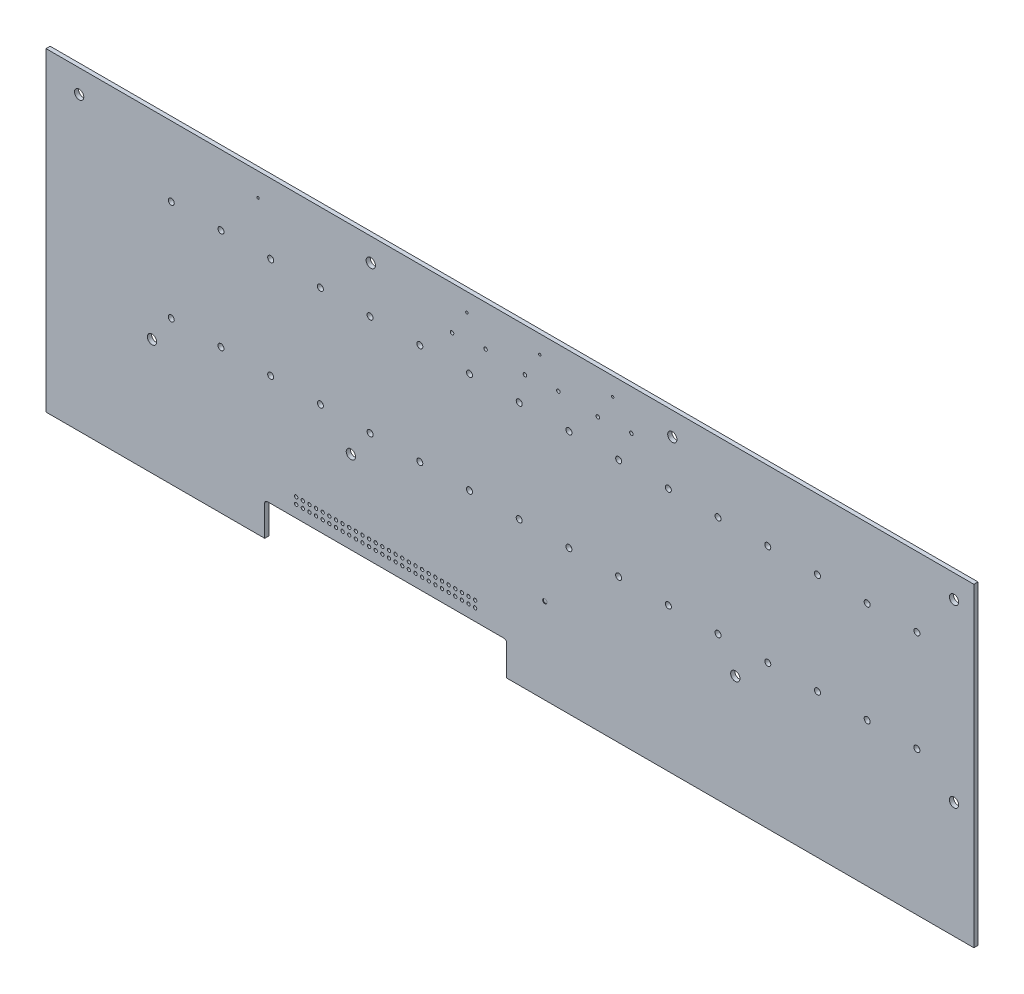
SolidWorks part; units mm, degrees
ref_plane "Front" through (0, 0, 0) normal (0, 0, 1) x (1, 0, 0)
ref_plane "Top" through (0, 0, 0) normal (0, 1, 0) x (1, 0, 0)
ref_plane "Right" through (0, 0, 0) normal (1, 0, 0) x (0, 0, -1)
sketch "Sketch1" plane through (0, 0, 0) normal (0, 0, 1) x (1, 0, 0)
  line L1 (0, 0) -> (355.6, 0)
  line L2 (0, 0) -> (0, -120.65)
  line L3 (0, -120.65) -> (355.6, -120.65)
  line L4 (355.6, 0) -> (355.6, -120.65)
  dimension "D1" = 120.65
  dimension "D2" = 355.6
extrude "Extrude1" add sketch "Sketch1" along normal blind 1.5748
sketch "DSPboard connector holes" plane through (0, 0, 1.5748) normal (0, 0, 1) x (1, 0, 0)
  line L0 (0, -120.65) -> (355.6, -120.65) construction
  line L1 (0, 0) -> (0, -120.65) construction
  circle A0 centre (48.006, -65.532) radius 1.15
  circle A1 centre (48.006, -26.802) radius 1.15
  dimension "D1" = 2.3
  dimension "D4" = 2.3
  dimension "D2" = 55.118
  dimension "D3" = 48.006
  dimension "D5" = 38.73
extrude "Cut-Extrude1" cut sketch "DSPboard connector holes" against normal blind 2.54
pattern_linear "LPattern1" count 16 spacing 19.05 along (1, 0, 0) of "Cut-Extrude1"
sketch "Sketch2" plane through (0, 0, 1.5748) normal (0, 0, 1) x (1, 0, 0)
  line L0 (0, -120.65) -> (355.6, -120.65) construction
  line L1 (0, 0) -> (0, -120.65) construction
  circle A0 centre (12.7, -8.89) radius 1.778
  circle A1 centre (124.46, -8.89) radius 1.778
  circle A2 centre (240.03, -8.89) radius 1.778
  circle A3 centre (347.98, -8.89) radius 1.778
  circle A4 centre (40.64, -76.2) radius 1.778
  circle A5 centre (116.84, -76.2) radius 1.778
  circle A6 centre (264.16, -76.2) radius 1.778
  circle A7 centre (347.98, -76.2) radius 1.778
  dimension "D1" = 3.556
  dimension "D4" = 3.556
  dimension "D5" = 3.556
  dimension "D6" = 3.556
  dimension "D10" = 3.556
  dimension "D11" = 3.556
  dimension "D12" = 3.556
  dimension "D13" = 3.556
  dimension "D2" = 111.76
  dimension "D3" = 12.7
  dimension "D7" = 124.46
  dimension "D8" = 240.03
  dimension "D9" = 347.98
  dimension "D14" = 44.45
  dimension "D15" = 40.64
  dimension "D16" = 116.84
  dimension "D17" = 264.16
  dimension "D18" = 347.98
extrude "PCB Mount holes" cut sketch "Sketch2" against normal blind 2.54
sketch "Sketch6" plane through (0, 0, 1.5748) normal (0, 0, 1) x (1, 0, 0)
  line L1 (0, 0) -> (0, -120.65) construction
  line L2 (355.6, 0) -> (0, 0) construction
  circle A4 centre (168.4383, -15.51) radius 0.675
  circle A5 centre (155.6083, -16.51) radius 0.675
  dimension "D2" = 16.51
  dimension "D8" = 1.35
  dimension "D9" = 1.35
  dimension "D11" = 12.83
  dimension "D14" = 155.6083
extrude "Peripheral-SATA" cut sketch "Sketch6" against normal blind 2.54
sketch "Sketch7" plane through (0, 0, 1.5748) normal (0, 0, 1) x (1, 0, 0)
  line L0 (355.6, 0) -> (0, 0) construction
  line L1 (0, 0) -> (0, -120.65) construction
  circle A0 centre (217.17, -6.985) radius 0.45
  circle A1 centre (189.23, -6.985) radius 0.45
  circle A2 centre (161.29, -6.985) radius 0.45
  circle A3 centre (81.28, -8.89) radius 0.45
  dimension "D1" = 0.9
  dimension "D4" = 0.8999
  dimension "D5" = 0.8999
  dimension "D6" = 0.8999
  dimension "D2" = 27.94
  dimension "D3" = 27.94
  dimension "D8" = 6.985
  dimension "D9" = 8.89
  dimension "D10" = 81.28
  dimension "D11" = 161.29
extrude "Off-board header holes" cut sketch "Sketch7" against normal blind 2.54
sketch "Sketch9" plane through (0, 0, 1.5748) normal (0, 0, 1) x (1, 0, 0)
  line L0 (0, -120.65) -> (355.6, -120.65) construction
  line L1 (84.836, -107.95) -> (175.514, -107.95)
  line L2 (83.82, -108.966) -> (83.82, -120.65)
  line L3 (83.82, -120.65) -> (176.53, -120.65)
  line L4 (176.53, -108.966) -> (176.53, -120.65)
  line L5 (0, 0) -> (0, -120.65) construction
  arc A0 (175.514, -107.95) -> (176.53, -108.966) centre (175.514, -108.966) cw
  arc A1 (83.82, -108.966) -> (84.836, -107.95) centre (84.836, -108.966) cw
  dimension "D1" = 1.016
  dimension "D2" = 1.016
  dimension "D3" = 92.71
  dimension "D4" = 83.82
  dimension "D5" = 12.7
extrude "NIC cutout" cut sketch "Sketch9" against normal blind 2.54
sketch "Sketch10" plane through (0, 0, 1.5748) normal (0, 0, 1) x (1, 0, 0)
  line L2 (175.514, -107.95) -> (84.836, -107.95) construction
  line L3 (176.53, -120.65) -> (176.53, -108.966) construction
  circle A0 centre (164.465, -100.838) radius 0.635
  dimension "D1" = 1.27
  dimension "D2" = 7.112
  dimension "D3" = 12.065
extrude "Header Holes" cut sketch "Sketch10" against normal blind 2.54
sketch "BGA mount pos" plane through (0, 0, 1.5748) normal (0, 0, 1) x (1, 0, 0)
  line L0 (0, 0) -> (0, -120.65) construction
  line L1 (176.53, -120.65) -> (355.6, -120.65) construction
  circle A0 centre (191.2, -87.85) radius 0.8381
  point P0 (191.2, -87.85)
  point P1 (0, -90.4568)
  dimension "D1" = 191.2
  dimension "D2" = 32.8
extrude "Cut-Extrude11" cut sketch "BGA mount pos" against normal blind 0.254
pattern_linear "LPattern3" count 28 spacing 2.54 along (-1, 0, 0) count 2 spacing 2.54 along (0, -1, 0) of "Header Holes"
pattern_linear "LPattern4" count 3 spacing 27.94 along (1, 0, 0) of "Peripheral-SATA"
